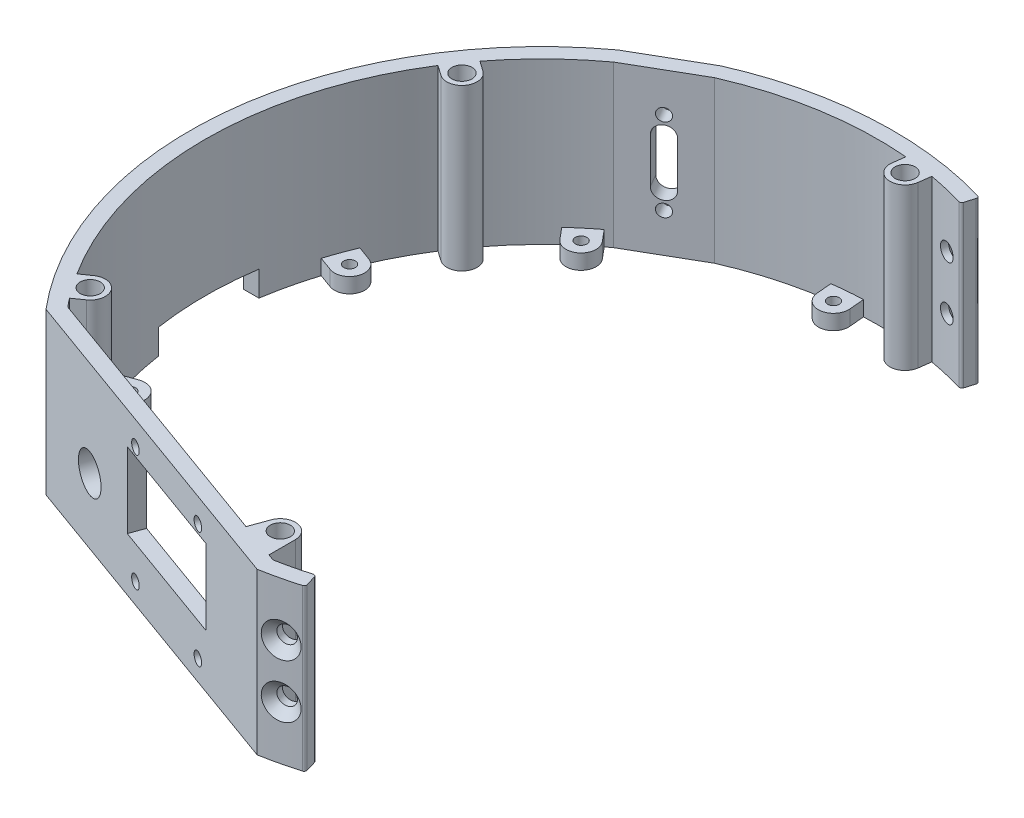
SolidWorks part; units mm, degrees
ref_plane "Front Plane" through (0, 0, 0) normal (0, 0, 1) x (1, 0, 0)
ref_plane "Top Plane" through (0, 0, 0) normal (0, 1, 0) x (1, 0, 0)
ref_plane "Right Plane" through (0, 0, 0) normal (1, 0, 0) x (0, 0, -1)
sketch "Sketch2" plane through (0, 0, 0) normal (0, 1, 0) x (1, 0, 0)
  line L0 (12.3, 68.9109) -> (12.3, -68.9109) construction
  line L1 (12.3, -68.9109) -> (-53.5286, -45.1076)
  line L2 (-28.3033, 64.0228) -> (-41.2937, 56.5228)
  line L3 (-51.7436, -42.5629) -> (12.3, -65.7208)
  line L4 (20.0782, 67.0587) -> (0, 0) construction
  line L5 (0, 0) -> (20.0782, -67.0587) construction
  line L6 (19.2177, 64.1847) -> (20.0782, 67.0587)
  line L7 (20.0782, -67.0587) -> (19.178, -64.0524)
  line L8 (-39.6526, 54.0062) -> (-26.9445, 61.3433)
  line L9 (-34.7985, 60.2728) -> (0, 0) construction
  line L10 (0, 0) -> (0, 50000) construction
  arc A0 (12.3, 68.9109) -> (-28.3033, 64.0228) centre (0, 0) ccw construction
  arc A1 (-53.5286, -45.1076) -> (-41.2937, 56.5228) centre (0, 0) cw
  arc A2 (12.3, 65.8613) -> (-26.9445, 61.3433) centre (0, 0) ccw
  arc A3 (12.3, 68.9109) -> (20.0782, 67.0587) centre (0, 0) cw
  arc A4 (12.3, 65.8613) -> (19.2177, 64.1847) centre (0, 0) cw
  arc A5 (12.3, -68.9109) -> (20.0782, -67.0587) centre (0, 0) ccw
  arc A6 (12.3, -65.7208) -> (19.178, -64.0524) centre (0, 0) ccw
  arc A7 (-39.6526, 54.0062) -> (-51.7436, -42.5629) centre (0, 0) ccw
  arc A8 (-41.2937, 56.5228) -> (12.3, -68.9109) centre (0, 0) ccw construction
  arc A9 (-28.3033, 64.0228) -> (12.3, 68.9109) centre (0, 0) cw
  point P18 (-33.2985, 57.6747)
  dimension "D1" = 70
  dimension "D4" = 3
  dimension "D6" = 8
  dimension "D2" = 12.3
  dimension "D3" = 3
  dimension "D5" = 70
  dimension "D7" = 8
  dimension "D8" = 3
  dimension "D9" = 15
  dimension "D10" = 30
extrude "Boss-Extrude1" add sketch "Sketch2" along normal blind 32
sketch "Sketch3" plane through (0, 0, 0) normal (0, 1, 0) x (1, 0, 0)
  line L0 (12.3, 68.9109) -> (12.3, -68.9109) construction
  line L1 (20.0782, -67.0587) -> (19.178, -64.0524) construction
  line L2 (19.2177, 64.1847) -> (20.0782, 67.0587) construction
  circle A0 centre (0, 0) radius 70 construction
  arc A1 (12.3, -68.9109) -> (20.0782, -67.0587) centre (0, 0) ccw
  arc A2 (12.3, 68.9109) -> (20.0782, 67.0587) centre (0, 0) cw
  point P8 (16.2155, -68.0959)
  point P9 (16.2155, 68.0959)
  dimension "D2" = 140
  dimension "D1" = 12.3
sketch3d "3DSketch1"
  line L0 (16.2155, 0, 68.0959) -> (16.2155, 32, 68.0959)
  line L1 (16.2155, 0, -68.0959) -> (16.2155, 32, -68.0959)
  arc A0 (12.3, 32, 68.9109) -> (20.0782, 32, 67.0587) centre (0, 32, 0) ccw construction
  arc A1 (20.0782, 32, -67.0587) -> (-28.3033, 32, -64.0228) centre (0, 32, 0) ccw construction
  point P6 (0, 102, 0)
  point P13 (0, 102, 0)
  point P14 (16.2155, 21.3333, 68.0959)
  point P15 (16.2155, 10.6667, 68.0959)
  point P16 (16.2155, 10.6667, -68.0959)
  point P17 (16.2155, 21.3333, -68.0959)
  dimension "D1" = 10.6667
  dimension "D2" = 21.3333
  dimension "D3" = 10.6667
  dimension "D4" = 21.3333
ref_plane "Plane1" through (16.2155, 0, -68.0959) normal (0.2317, 0, -0.9728) x (-0.9728, 0, -0.2317)
ref_plane "Plane2" through (16.2155, 0, 68.0959) normal (0.2317, 0, 0.9728) x (0.9728, 0, -0.2317)
sketch "Sketch4" plane through (16.2155, 0, -68.0959) normal (0.2317, 0, -0.9728) x (-0.9728, 0, -0.2317)
  line L0 (0, 0) -> (0, 32) construction
  circle A0 centre (0, 21.3333) radius 1.65 construction
  circle A1 centre (0, 10.6667) radius 1.65 construction
  point P0 (0, 21.3333)
  point P4 (0, 10.6667)
  dimension "D1" = 3.3
  dimension "D2" = 10.6667
  dimension "D3" = 21.3333
sketch "Sketch5" plane through (16.2155, 0, 68.0959) normal (0.2317, 0, 0.9728) x (0.9728, 0, -0.2317)
  line L0 (0, 0) -> (0, 32) construction
  circle A0 centre (0, 21.3333) radius 1.65 construction
  circle A1 centre (0, 10.6667) radius 1.65 construction
  point P0 (0, 21.3333)
  point P4 (0, 10.6667)
  dimension "D1" = 3.3
  dimension "D2" = 10.6667
  dimension "D3" = 21.3333
fillet "Fillet1" radius 0.5 4 edges at (20.0782, 16, -67.0587) (19.2177, 16, -64.1847) (19.178, 16, 64.0524) (20.0782, 16, 67.0587)
sketch "Sketch6" plane through (0, 0, 0) normal (1, 0, 0) x (0, 0, -1)
  line L0 (70, 0) -> (-70, 0) construction
  line L1 (-10, 0) -> (10, 0)
  line L2 (-10, 0) -> (-10, 5)
  line L3 (-10, 5) -> (10, 5)
  line L4 (10, 0) -> (10, 5)
  dimension "D1" = 10
  dimension "D2" = 5
  dimension "D3" = 20
extrude "Cut-Extrude3" cut sketch "Sketch6" against normal through all
sketch "Sketch7" plane through (-20.6143, 0, 57.0092) normal (-0.34, 0, 0.9404) x (0.9404, 0, 0.34)
  line L0 (5, 29.3) -> (5, 2) construction
  line L1 (-8.65, 29.3) -> (18.65, 29.3) construction
  line L2 (-8.65, 29.3) -> (-8.65, 2) construction
  line L3 (-8.65, 2) -> (18.65, 2) construction
  line L4 (18.65, 29.3) -> (18.65, 2) construction
  line L5 (-8.65, 29.3) -> (18.65, 2) construction
  line L6 (-8.65, 2) -> (18.65, 29.3) construction
  line L7 (-35, 0) -> (35, 0) construction
  line L8 (-8.05, 25.58) -> (18.05, 25.58)
  line L9 (-8.05, 25.58) -> (-8.05, 10.58)
  line L10 (-8.05, 10.58) -> (18.05, 10.58)
  line L11 (18.05, 25.58) -> (18.05, 10.58)
  line L12 (-8.05, 25.58) -> (18.05, 10.58) construction
  line L13 (-8.05, 10.58) -> (18.05, 25.58) construction
  line L14 (-5.35, 27.25) -> (15.35, 27.25) construction
  line L15 (-5.35, 27.25) -> (-5.35, 4.05) construction
  line L16 (-5.35, 4.05) -> (15.35, 4.05) construction
  line L17 (15.35, 27.25) -> (15.35, 4.05) construction
  line L18 (70, 0) -> (-70, 0) construction
  circle A0 centre (-5.35, 27.25) radius 1.25
  circle A1 centre (15.35, 27.25) radius 1.25
  circle A2 centre (15.35, 4.05) radius 1.25
  circle A3 centre (-5.35, 4.05) radius 1.25
  circle A4 centre (-20.5, 13) radius 3.75
  point P0 (5, 15.65)
  point P5 (5, 18.08)
  point P24 (0, 0)
  dimension "D9" = 2.5
  dimension "D13" = 7.5
  dimension "D14" = 13
  dimension "D15" = 20.5
  dimension "D1" = 27.3
  dimension "D2" = 27.3
  dimension "D3" = 26.1
  dimension "D4" = 15
  dimension "D5" = 2.05
  dimension "D6" = 3.3
  dimension "D7" = 20.7
  dimension "D8" = 11.22
  dimension "D10" = 5
  dimension "D11" = 2
  dimension "D12" = 23.2
extrude "Cut-Extrude4" cut sketch "Sketch7" against normal blind 8
sketch "Sketch8" plane through (0, 0, 0) normal (0, 1, 0) x (1, 0, 0)
  line L0 (8.7453, 66.4268) -> (8.4189, 63.9482) construction
  line L1 (11.7108, 65.9686) -> (11.3933, 63.5566)
  line L2 (5.7621, 66.7518) -> (5.4446, 64.3398)
  line L3 (5.4446, 64.3398) -> (11.3933, 63.5566) construction
  line L4 (-54.8832, 38.4296) -> (-52.8353, 36.9957) construction
  line L5 (-53.1074, 40.8485) -> (-51.1146, 39.4531)
  line L6 (-56.5489, 35.9336) -> (-54.556, 34.5382)
  line L7 (-54.556, 34.5382) -> (-51.1146, 39.4531) construction
  line L8 (-54.8832, -38.4296) -> (-52.8353, -36.9957) construction
  line L9 (-56.5489, -35.9336) -> (-54.556, -34.5382)
  line L10 (-53.1074, -40.8485) -> (-51.1146, -39.4531)
  line L11 (-51.1146, -39.4531) -> (-54.556, -34.5382) construction
  line L12 (0, 1.3173) -> (0, 50001.3173) construction
  line L13 (11, -65.2507) -> (11, -60)
  line L14 (12.3, -65.7208) -> (-51.7436, -42.5629) construction
  line L15 (5.1788, -58.9799) -> (3.8466, -62.6641)
  line L16 (8, -60) -> (6.6678, -63.6842) construction
  line L17 (11, -65.2507) -> (3.8466, -62.6641)
  arc A0 (-53.1074, -40.8485) -> (-56.5489, -35.9336) centre (0, 0) cw
  arc A1 (18.7417, 64.3253) -> (-26.9445, 61.3433) centre (0, 0) ccw construction
  arc A2 (5.7621, 66.7518) -> (11.7108, 65.9686) centre (0, 0) cw
  circle A3 centre (8.4189, 63.9482) radius 1.65
  arc A4 (11.3933, 63.5566) -> (5.4446, 64.3398) centre (8.4189, 63.9482) cw
  arc A5 (-56.5489, 35.9336) -> (-53.1074, 40.8485) centre (0, 0) cw
  circle A6 centre (-52.8353, 36.9957) radius 1.65
  arc A7 (-51.1146, 39.4531) -> (-54.556, 34.5382) centre (-52.8353, 36.9957) cw
  circle A8 centre (-52.8353, -36.9957) radius 1.65
  arc A9 (-54.556, -34.5382) -> (-51.1146, -39.4531) centre (-52.8353, -36.9957) cw
  arc A10 (11, -60) -> (5.1788, -58.9799) centre (8, -60) ccw
  circle A11 centre (8, -60) radius 1.65
  circle A12 centre (0, 0) radius 67 construction
  point P12 (8.7453, 66.4268)
  point P15 (8.7453, 66.4268)
  point P17 (8.4189, 63.9482)
  point P24 (-54.8832, 38.4296)
  point P26 (-54.8832, 38.4296)
  point P27 (-52.8353, 36.9957)
  point P43 (-52.8353, -36.9957)
  dimension "D1" = 3.3
  dimension "D2" = 6
  dimension "D3" = 3.3
  dimension "D5" = 3.3
  dimension "D13" = 3
  dimension "D14" = 3.3
  dimension "D4" = 6
  dimension "D6" = 6
  dimension "D7" = 2.5
  dimension "D8" = 7.5
  dimension "D9" = 55
  dimension "D10" = 55
  dimension "D11" = 2.5
  dimension "D12" = 2.5
  dimension "D15" = 60
  dimension "D16" = 8
extrude "Boss-Extrude2" add sketch "Sketch8" along normal up to surface (32 mm away) up to face at (-6.541, 32, -1.7)
sketch "Sketch13" plane through (0, 0, 0) normal (0, 1, 0) x (1, 0, 0)
  line L0 (-62.8963, 22.8924) -> (-60.0772, 21.8663) construction
  line L1 (-59.0511, 24.6854) -> (-61.1032, 19.0472) construction
  line L2 (-61.1032, 19.0472) -> (-63.9223, 20.0733)
  line L3 (-61.8702, 25.7114) -> (-59.0511, 24.6854)
  line L4 (0, 0) -> (0, 50000) construction
  line L5 (-62.8963, -22.8924) -> (-60.0772, -21.8663) construction
  line L6 (-61.1032, -19.0472) -> (-59.0511, -24.6854) construction
  line L7 (-59.0511, -24.6854) -> (-61.8702, -25.7114)
  line L8 (-63.9223, -20.0733) -> (-61.1032, -19.0472)
  line L9 (-5.8336, 66.6781) -> (-5.5721, 63.6895) construction
  line L10 (-2.5835, 63.951) -> (-8.5607, 63.4281) construction
  line L11 (-8.5607, 63.4281) -> (-8.8222, 66.4166)
  line L12 (-2.845, 66.9396) -> (-2.5835, 63.951)
  line L13 (-43.0236, 51.2735) -> (-41.0952, 48.9754) construction
  line L14 (-38.7971, 50.9037) -> (-43.3933, 47.047) construction
  line L15 (-43.3933, 47.047) -> (-45.3217, 49.3451)
  line L16 (-40.7254, 53.2019) -> (-38.7971, 50.9037)
  line L17 (1.0254, -61.6439) -> (2.0455, -58.8227) construction
  line L18 (-0.7757, -57.8026) -> (4.8667, -59.8428) construction
  line L19 (4.8667, -59.8428) -> (3.8466, -62.6641)
  line L20 (-1.7959, -60.6238) -> (-0.7757, -57.8026)
  line L21 (3.8466, -62.6641) -> (-1.7959, -60.6238)
  line L22 (5.1788, -58.9799) -> (3.8466, -62.6641) construction
  line L25 (3.8466, -62.6641) -> (-51.7436, -42.5629) construction
  circle A0 centre (0, 0) radius 67 construction
  arc A1 (-63.9223, 20.0733) -> (-61.8702, 25.7114) centre (0, 0) cw
  arc A2 (-61.1032, 19.0472) -> (-59.0511, 24.6854) centre (-60.0772, 21.8663) ccw
  circle A3 centre (-60.0772, 21.8663) radius 1.15
  arc A4 (-61.8702, -25.7114) -> (-63.9223, -20.0733) centre (0, 0) cw
  arc A5 (-59.0511, -24.6854) -> (-61.1032, -19.0472) centre (-60.0772, -21.8663) ccw
  circle A6 centre (-60.0772, -21.8663) radius 1.15
  arc A7 (-8.8222, 66.4166) -> (-2.845, 66.9396) centre (0, 0) cw
  arc A8 (-8.5607, 63.4281) -> (-2.5835, 63.951) centre (-5.5721, 63.6895) ccw
  circle A9 centre (-5.5721, 63.6895) radius 1.15
  arc A10 (-45.3217, 49.3451) -> (-40.7254, 53.2019) centre (0, 0) cw
  arc A11 (-43.3933, 47.047) -> (-38.7971, 50.9037) centre (-41.0952, 48.9754) ccw
  circle A12 centre (-41.0952, 48.9754) radius 1.15
  arc A14 (4.8667, -59.8428) -> (-0.7757, -57.8026) centre (2.0455, -58.8227) ccw
  circle A15 centre (2.0455, -58.8227) radius 1.15
  point P10 (-60.0772, 21.8663)
  point P20 (-60.0772, -21.8663)
  point P30 (-5.5721, 63.6895)
  point P41 (-41.0952, 48.9754)
  point P52 (2.0455, -58.8227)
  dimension "D1" = 134
  dimension "D2" = 3
  dimension "D3" = 2.3
  dimension "D6" = 3
  dimension "D7" = 2.3
  dimension "D10" = 3
  dimension "D11" = 2.3
  dimension "D14" = 3
  dimension "D15" = 2.3
  dimension "D18" = 3
  dimension "D19" = 2.3
  dimension "D4" = 3
  dimension "D5" = 70
  dimension "D8" = 3
  dimension "D9" = 70
  dimension "D12" = 3
  dimension "D13" = 5
  dimension "D16" = 3
  dimension "D17" = 40
  dimension "D20" = 3
  dimension "D21" = 2.0455
  dimension "D22" = 58.8227
extrude "Boss-Extrude3" add sketch "Sketch13" along normal blind 3
hole_wizard "CSK for M3 Flat Head Machine Screw1" positions "Sketch4" profile "Sketch16" countersink size "M3" standard "ANSI Metric"
sketch "Sketch16" plane through (16.2155, 21.3333, -68.0959) normal (0, 1, 0) x (-0.9728, 0, -0.2317)
  line L0 (0, 0) -> (0, 21.0215)
  line L1 (0, 21.0215) -> (1.7, 20)
  line L2 (1.7, 20) -> (1.7, 1.675)
  line L3 (1.7, 1.675) -> (3.375, 0)
  line L5 (3.375, 0) -> (0, 0)
  line L6 (-1.7, 1.675) -> (-3.375, 0) construction
  line L10 (0, 21.0215) -> (-1.7, 20) construction
  line L11 (0, -6.35) -> (0, 107.95) construction
  dimension "Hole Dia." = 3.4
  dimension "Hole Depth" = 20
  dimension "Near C'Sink Dia." = 6.75
  dimension "Near C'Sink Angle" = 90
  dimension "Drill Angle" = 118
hole_wizard "CSK for M3 Flat Head Machine Screw2" positions "Sketch5" profile "Sketch17" countersink size "M3" standard "ANSI Metric"
sketch "Sketch17" plane through (16.2155, 21.3333, 68.0959) normal (0, 1, 0) x (0.9728, 0, -0.2317)
  line L0 (0, 0) -> (0, 21.0215)
  line L1 (0, 21.0215) -> (1.7, 20)
  line L2 (1.7, 20) -> (1.7, 1.675)
  line L3 (1.7, 1.675) -> (3.375, 0)
  line L5 (3.375, 0) -> (0, 0)
  line L6 (-1.7, 1.675) -> (-3.375, 0) construction
  line L10 (0, 21.0215) -> (-1.7, 20) construction
  line L11 (0, -6.35) -> (0, 107.95) construction
  dimension "Hole Dia." = 3.4
  dimension "Hole Depth" = 20
  dimension "Near C'Sink Dia." = 6.75
  dimension "Near C'Sink Angle" = 90
  dimension "Drill Angle" = 118
sketch "Sketch18" plane through (0, 32, 0) normal (0, 1, 0) x (1, 0, 0)
  circle A0 centre (8.4189, 63.9482) radius 2
  circle A1 centre (-52.8353, 36.9957) radius 2
  circle A2 centre (-52.8353, -36.9957) radius 2
  circle A3 centre (8, -60) radius 2
  dimension "D1" = 4
extrude "Cut-Extrude5" cut sketch "Sketch18" against normal blind 4.78
sketch "Sketch19" plane through (-34.7985, 0, -60.2728) normal (-0.5, 0, -0.866) x (-0.866, 0, 0.5)
  line L0 (0, 24.25) -> (0, 7.75) construction
  line L1 (0, 11.5) -> (0, 20.5) construction
  line L8 (-2, 11.5) -> (-2, 20.5)
  line L9 (2, 11.5) -> (2, 20.5)
  circle A0 centre (0, 24.25) radius 1.25
  circle A1 centre (0, 7.75) radius 1.25
  arc A2 (-2, 11.5) -> (2, 11.5) centre (0, 11.5) ccw
  arc A3 (2, 20.5) -> (-2, 20.5) centre (0, 20.5) ccw
  point P5 (0, 16)
  point P6 (0, 16)
  point P9 (0, 16)
  point P14 (0, 0)
  point P15 (0, 22.5)
  dimension "D3" = 2.5
  dimension "D4" = 13
  dimension "D5" = 2
  dimension "D1" = 16.5
  dimension "D2" = 16
extrude "Cut-Extrude6" cut sketch "Sketch19" against normal blind 10
